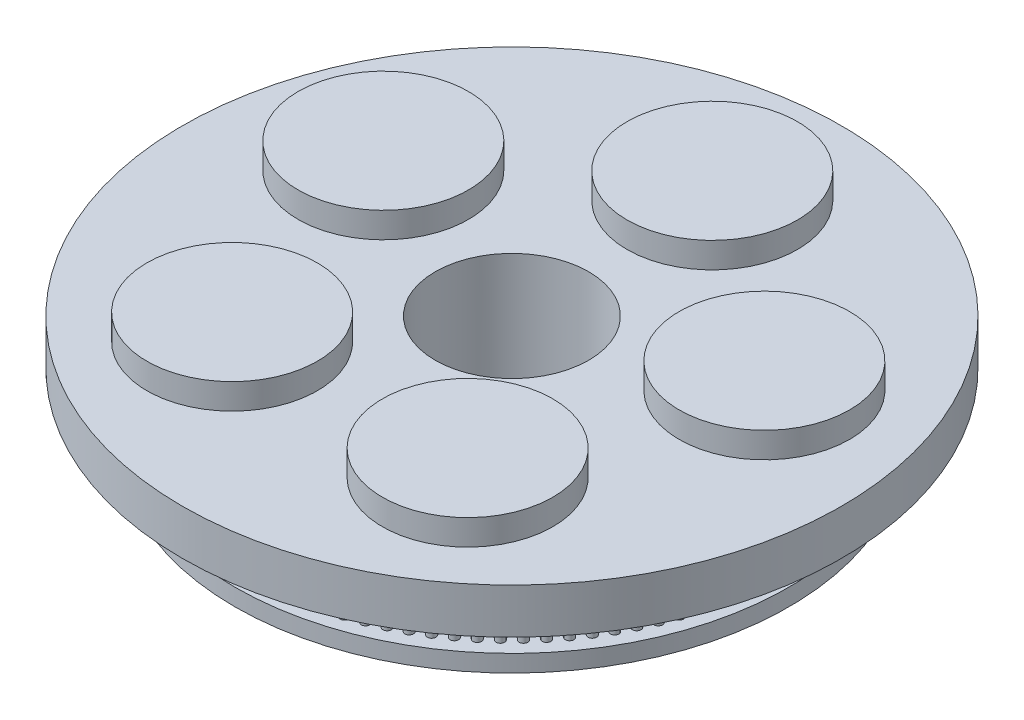
SolidWorks part; units mm, degrees
ref_plane "前基準面" through (0, 0, 0) normal (0, 0, 1) x (1, 0, 0)
ref_plane "上基準面" through (0, 0, 0) normal (0, 1, 0) x (1, 0, 0)
ref_plane "右基準面" through (0, 0, 0) normal (1, 0, 0) x (0, 0, -1)
sketch "草圖1" plane through (0, 0, 0) normal (0, 1, 0) x (1, 0, 0)
  circle A0 centre (0, 0) radius 38.66
  circle A1 centre (0, 0) radius 9
  dimension "D1" = 77.32
  dimension "D2" = 18
extrude "填料-伸長1" add sketch "草圖1" along normal blind 5.3
sketch "草圖3" plane through (0, 0, 0) normal (0, 0, 1) x (1, 0, 0)
  line L0 (0, 0) -> (0, 14.4931) construction
sketch "草圖2" plane through (0, 5.3, 0) normal (0, 1, 0) x (1, 0, 0)
  circle A0 centre (0, 23.5) radius 10
  dimension "D1" = 20
  dimension "D2" = 23.5
extrude "填料-伸長2" add sketch "草圖2" along normal blind 3
pattern_circular "環狀複製排列1" count 5 over 360 about axis through (0, 0, 0) along (0, 1, 0) of "填料-伸長2" reverse direction yes
sketch "草圖4" plane through (0, 0, 0) normal (0, -1, 0) x (1, 0, 0)
  line L0 (0, 0) -> (0, 38.66) construction
  line L1 (-0.5, 30.56) -> (-0.5, 29.9958) construction
  line L2 (-0.5, 30.56) -> (-0.5, 30.41)
  line L3 (0.5, 30.56) -> (0.5, 30.41)
  line L4 (1.4199, 30.5311) -> (1.4104, 30.3814)
  line L5 (2.4179, 30.4683) -> (2.4085, 30.3186)
  line L6 (3.3341, 30.3817) -> (3.3153, 30.2329)
  line L7 (4.3262, 30.2564) -> (4.3074, 30.1075)
  line L8 (5.2352, 30.1124) -> (5.2071, 29.965)
  line L9 (6.2175, 29.925) -> (6.1894, 29.7777)
  line L10 (7.1157, 29.7242) -> (7.0784, 29.579)
  line L11 (8.0843, 29.4756) -> (8.047, 29.3303)
  line L12 (8.968, 29.2188) -> (8.9217, 29.0761)
  line L13 (9.9191, 28.9098) -> (9.8727, 28.7671)
  line L14 (10.785, 28.598) -> (10.7298, 28.4586)
  line L15 (11.7148, 28.2299) -> (11.6596, 28.0904)
  line L16 (12.5594, 27.8644) -> (12.4955, 27.7287)
  line L17 (13.4642, 27.4386) -> (13.4004, 27.3029)
  line L18 (14.2842, 27.0208) -> (14.212, 26.8894)
  line L19 (15.1605, 26.5391) -> (15.0883, 26.4076)
  line L20 (15.9527, 26.0706) -> (15.8723, 25.9439)
  line L21 (16.797, 25.5347) -> (16.7167, 25.4081)
  line L22 (17.5582, 25.0175) -> (17.47, 24.8961)
  line L23 (18.3672, 24.4297) -> (18.2791, 24.3083)
  line L24 (19.0944, 23.8656) -> (18.9988, 23.75)
  line L25 (19.8649, 23.2282) -> (19.7693, 23.1126)
  line L26 (20.5553, 22.6196) -> (20.4526, 22.5102)
  line L27 (21.2842, 21.935) -> (21.1816, 21.8257)
  line L28 (21.935, 21.2842) -> (21.8257, 21.1816)
  line L29 (22.6196, 20.5553) -> (22.5102, 20.4526)
  line L30 (23.2282, 19.8649) -> (23.1126, 19.7693)
  line L31 (23.8656, 19.0944) -> (23.75, 18.9988)
  line L32 (24.4297, 18.3672) -> (24.3083, 18.2791)
  line L33 (25.0175, 17.5582) -> (24.8961, 17.47)
  line L34 (25.5347, 16.797) -> (25.4081, 16.7167)
  line L35 (26.0706, 15.9527) -> (25.9439, 15.8723)
  line L36 (26.5391, 15.1605) -> (26.4076, 15.0883)
  line L37 (27.0208, 14.2842) -> (26.8894, 14.212)
  line L38 (27.4386, 13.4642) -> (27.3029, 13.4004)
  line L39 (27.8644, 12.5594) -> (27.7287, 12.4955)
  line L40 (28.2299, 11.7148) -> (28.0904, 11.6596)
  line L41 (28.598, 10.785) -> (28.4586, 10.7298)
  line L42 (28.9098, 9.9191) -> (28.7671, 9.8727)
  line L43 (29.2188, 8.968) -> (29.0761, 8.9217)
  line L44 (29.4756, 8.0843) -> (29.3303, 8.047)
  line L45 (29.7242, 7.1157) -> (29.579, 7.0784)
  line L46 (29.925, 6.2175) -> (29.7777, 6.1894)
  line L47 (30.1124, 5.2352) -> (29.965, 5.2071)
  line L48 (30.2564, 4.3262) -> (30.1075, 4.3074)
  line L49 (30.3817, 3.3341) -> (30.2329, 3.3153)
  line L50 (30.4683, 2.4179) -> (30.3186, 2.4085)
  line L51 (30.5311, 1.4199) -> (30.3814, 1.4104)
  line L52 (30.56, 0.5) -> (30.41, 0.5)
  line L53 (30.56, -0.5) -> (30.41, -0.5)
  line L54 (30.5311, -1.4199) -> (30.3814, -1.4104)
  line L55 (30.4683, -2.4179) -> (30.3186, -2.4085)
  line L56 (30.3817, -3.3341) -> (30.2329, -3.3153)
  line L57 (30.2564, -4.3262) -> (30.1075, -4.3074)
  line L58 (30.1124, -5.2352) -> (29.965, -5.2071)
  line L59 (29.925, -6.2175) -> (29.7777, -6.1894)
  line L60 (29.7242, -7.1157) -> (29.579, -7.0784)
  line L61 (29.4756, -8.0843) -> (29.3303, -8.047)
  line L62 (29.2188, -8.968) -> (29.0761, -8.9217)
  line L63 (28.9098, -9.9191) -> (28.7671, -9.8727)
  line L64 (28.598, -10.785) -> (28.4586, -10.7298)
  line L65 (28.2299, -11.7148) -> (28.0904, -11.6596)
  line L66 (27.8644, -12.5594) -> (27.7287, -12.4955)
  line L67 (27.4386, -13.4642) -> (27.3029, -13.4004)
  line L68 (27.0208, -14.2842) -> (26.8894, -14.212)
  line L69 (26.5391, -15.1605) -> (26.4076, -15.0883)
  line L70 (26.0706, -15.9527) -> (25.9439, -15.8723)
  line L71 (25.5347, -16.797) -> (25.4081, -16.7167)
  line L72 (25.0175, -17.5582) -> (24.8961, -17.47)
  line L73 (24.4297, -18.3672) -> (24.3083, -18.2791)
  line L74 (23.8656, -19.0944) -> (23.75, -18.9988)
  line L75 (23.2282, -19.8649) -> (23.1126, -19.7693)
  line L76 (22.6196, -20.5553) -> (22.5102, -20.4526)
  line L77 (21.935, -21.2842) -> (21.8257, -21.1816)
  line L78 (21.2842, -21.935) -> (21.1816, -21.8257)
  line L79 (20.5553, -22.6196) -> (20.4526, -22.5102)
  line L80 (19.8649, -23.2282) -> (19.7693, -23.1126)
  line L81 (19.0944, -23.8656) -> (18.9988, -23.75)
  line L82 (18.3672, -24.4297) -> (18.2791, -24.3083)
  line L83 (17.5582, -25.0175) -> (17.47, -24.8961)
  line L84 (16.797, -25.5347) -> (16.7167, -25.4081)
  line L85 (15.9527, -26.0706) -> (15.8723, -25.9439)
  line L86 (15.1605, -26.5391) -> (15.0883, -26.4076)
  line L87 (14.2842, -27.0208) -> (14.212, -26.8894)
  line L88 (13.4642, -27.4386) -> (13.4004, -27.3029)
  line L89 (12.5594, -27.8644) -> (12.4955, -27.7287)
  line L90 (11.7148, -28.2299) -> (11.6596, -28.0904)
  line L91 (10.785, -28.598) -> (10.7298, -28.4586)
  line L92 (9.9191, -28.9098) -> (9.8727, -28.7671)
  line L93 (8.968, -29.2188) -> (8.9217, -29.0761)
  line L94 (8.0843, -29.4756) -> (8.047, -29.3303)
  line L95 (7.1157, -29.7242) -> (7.0784, -29.579)
  line L96 (6.2175, -29.925) -> (6.1894, -29.7777)
  line L97 (5.2352, -30.1124) -> (5.2071, -29.965)
  line L98 (4.3262, -30.2564) -> (4.3074, -30.1075)
  line L99 (3.3341, -30.3817) -> (3.3153, -30.2329)
  line L100 (2.4179, -30.4683) -> (2.4085, -30.3186)
  line L101 (1.4199, -30.5311) -> (1.4104, -30.3814)
  line L102 (0.5, -30.56) -> (0.5, -30.41)
  line L103 (-0.5, -30.56) -> (-0.5, -30.41)
  line L104 (-1.4199, -30.5311) -> (-1.4104, -30.3814)
  line L105 (-2.4179, -30.4683) -> (-2.4085, -30.3186)
  line L106 (-3.3341, -30.3817) -> (-3.3153, -30.2329)
  line L107 (-4.3262, -30.2564) -> (-4.3074, -30.1075)
  line L108 (-5.2352, -30.1124) -> (-5.2071, -29.965)
  line L109 (-6.2175, -29.925) -> (-6.1894, -29.7777)
  line L110 (-7.1157, -29.7242) -> (-7.0784, -29.579)
  line L111 (-8.0843, -29.4756) -> (-8.047, -29.3303)
  line L112 (-8.968, -29.2188) -> (-8.9217, -29.0761)
  line L113 (-9.9191, -28.9098) -> (-9.8727, -28.7671)
  line L114 (-10.785, -28.598) -> (-10.7298, -28.4586)
  line L115 (-11.7148, -28.2299) -> (-11.6596, -28.0904)
  line L116 (-12.5594, -27.8644) -> (-12.4955, -27.7287)
  line L117 (-13.4642, -27.4386) -> (-13.4004, -27.3029)
  line L118 (-14.2842, -27.0208) -> (-14.212, -26.8894)
  line L119 (-15.1605, -26.5391) -> (-15.0883, -26.4076)
  line L120 (-15.9527, -26.0706) -> (-15.8723, -25.9439)
  line L121 (-16.797, -25.5347) -> (-16.7167, -25.4081)
  line L122 (-17.5582, -25.0175) -> (-17.47, -24.8961)
  line L123 (-18.3672, -24.4297) -> (-18.2791, -24.3083)
  line L124 (-19.0944, -23.8656) -> (-18.9988, -23.75)
  line L125 (-19.8649, -23.2282) -> (-19.7693, -23.1126)
  line L126 (-20.5553, -22.6196) -> (-20.4526, -22.5102)
  line L127 (-21.2842, -21.935) -> (-21.1816, -21.8257)
  line L128 (-21.935, -21.2842) -> (-21.8257, -21.1816)
  line L129 (-22.6196, -20.5553) -> (-22.5102, -20.4526)
  line L130 (-23.2282, -19.8649) -> (-23.1126, -19.7693)
  line L131 (-23.8656, -19.0944) -> (-23.75, -18.9988)
  line L132 (-24.4297, -18.3672) -> (-24.3083, -18.2791)
  line L133 (-25.0175, -17.5582) -> (-24.8961, -17.47)
  line L134 (-25.5347, -16.797) -> (-25.4081, -16.7167)
  line L135 (-26.0706, -15.9527) -> (-25.9439, -15.8723)
  line L136 (-26.5391, -15.1605) -> (-26.4076, -15.0883)
  line L137 (-27.0208, -14.2842) -> (-26.8894, -14.212)
  line L138 (-27.4386, -13.4642) -> (-27.3029, -13.4004)
  line L139 (-27.8644, -12.5594) -> (-27.7287, -12.4955)
  line L140 (-28.2299, -11.7148) -> (-28.0904, -11.6596)
  line L141 (-28.598, -10.785) -> (-28.4586, -10.7298)
  line L142 (-28.9098, -9.9191) -> (-28.7671, -9.8727)
  line L143 (-29.2188, -8.968) -> (-29.0761, -8.9217)
  line L144 (-29.4756, -8.0843) -> (-29.3303, -8.047)
  line L145 (-29.7242, -7.1157) -> (-29.579, -7.0784)
  line L146 (-29.925, -6.2175) -> (-29.7777, -6.1894)
  line L147 (-30.1124, -5.2352) -> (-29.965, -5.2071)
  line L148 (-30.2564, -4.3262) -> (-30.1075, -4.3074)
  line L149 (-30.3817, -3.3341) -> (-30.2329, -3.3153)
  line L150 (-30.4683, -2.4179) -> (-30.3186, -2.4085)
  line L151 (-30.5311, -1.4199) -> (-30.3814, -1.4104)
  line L152 (-30.56, -0.5) -> (-30.41, -0.5)
  line L153 (-30.56, 0.5) -> (-30.41, 0.5)
  line L154 (-30.5311, 1.4199) -> (-30.3814, 1.4104)
  line L155 (-30.4683, 2.4179) -> (-30.3186, 2.4085)
  line L156 (-30.3817, 3.3341) -> (-30.2329, 3.3153)
  line L157 (-30.2564, 4.3262) -> (-30.1075, 4.3074)
  line L158 (-30.1124, 5.2352) -> (-29.965, 5.2071)
  line L159 (-29.925, 6.2175) -> (-29.7777, 6.1894)
  line L160 (-29.7242, 7.1157) -> (-29.579, 7.0784)
  line L161 (-29.4756, 8.0843) -> (-29.3303, 8.047)
  line L162 (-29.2188, 8.968) -> (-29.0761, 8.9217)
  line L163 (-28.9098, 9.9191) -> (-28.7671, 9.8727)
  line L164 (-28.598, 10.785) -> (-28.4586, 10.7298)
  line L165 (-28.2299, 11.7148) -> (-28.0904, 11.6596)
  line L166 (-27.8644, 12.5594) -> (-27.7287, 12.4955)
  line L167 (-27.4386, 13.4642) -> (-27.3029, 13.4004)
  line L168 (-27.0208, 14.2842) -> (-26.8894, 14.212)
  line L169 (-26.5391, 15.1605) -> (-26.4076, 15.0883)
  line L170 (-26.0706, 15.9527) -> (-25.9439, 15.8723)
  line L171 (-25.5347, 16.797) -> (-25.4081, 16.7167)
  line L172 (-25.0175, 17.5582) -> (-24.8961, 17.47)
  line L173 (-24.4297, 18.3672) -> (-24.3083, 18.2791)
  line L174 (-23.8656, 19.0944) -> (-23.75, 18.9988)
  line L175 (-23.2282, 19.8649) -> (-23.1126, 19.7693)
  line L176 (-22.6196, 20.5553) -> (-22.5102, 20.4526)
  line L177 (-21.935, 21.2842) -> (-21.8257, 21.1816)
  line L178 (-21.2842, 21.935) -> (-21.1816, 21.8257)
  line L179 (-20.5553, 22.6196) -> (-20.4526, 22.5102)
  line L180 (-19.8649, 23.2282) -> (-19.7693, 23.1126)
  line L181 (-19.0944, 23.8656) -> (-18.9988, 23.75)
  line L182 (-18.3672, 24.4297) -> (-18.2791, 24.3083)
  line L183 (-17.5582, 25.0175) -> (-17.47, 24.8961)
  line L184 (-16.797, 25.5347) -> (-16.7167, 25.4081)
  line L185 (-15.9527, 26.0706) -> (-15.8723, 25.9439)
  line L186 (-15.1605, 26.5391) -> (-15.0883, 26.4076)
  line L187 (-14.2842, 27.0208) -> (-14.212, 26.8894)
  line L188 (-13.4642, 27.4386) -> (-13.4004, 27.3029)
  line L189 (-12.5594, 27.8644) -> (-12.4955, 27.7287)
  line L190 (-11.7148, 28.2299) -> (-11.6596, 28.0904)
  line L191 (-10.785, 28.598) -> (-10.7298, 28.4586)
  line L192 (-9.9191, 28.9098) -> (-9.8727, 28.7671)
  line L193 (-8.968, 29.2188) -> (-8.9217, 29.0761)
  line L194 (-8.0843, 29.4756) -> (-8.047, 29.3303)
  line L195 (-7.1157, 29.7242) -> (-7.0784, 29.579)
  line L196 (-6.2175, 29.925) -> (-6.1894, 29.7777)
  line L197 (-5.2352, 30.1124) -> (-5.2071, 29.965)
  line L198 (-4.3262, 30.2564) -> (-4.3074, 30.1075)
  line L199 (-3.3341, 30.3817) -> (-3.3153, 30.2329)
  line L200 (-2.4179, 30.4683) -> (-2.4085, 30.3186)
  line L201 (-1.4199, 30.5311) -> (-1.4104, 30.3814)
  circle A0 centre (0, 0) radius 30.56 construction
  circle A1 centre (0, 0) radius 30
  circle A2 centre (0, 0) radius 38.66 construction
  arc A3 (0.5, 30.5559) -> (-0.5, 30.56) centre (0, 30.56) ccw
  arc A4 (-0.5, 30.41) -> (-0.9112, 29.9862) centre (-0.924, 30.41) cw
  arc A5 (2.4176, 30.4642) -> (1.4199, 30.5311) centre (1.9189, 30.4997) ccw
  arc A6 (1.4104, 30.3814) -> (0.9735, 29.9842) centre (0.9872, 30.408) cw
  arc A7 (0.5, 30.41) -> (0.9112, 29.9862) centre (0.924, 30.41) ccw
  arc A8 (2.4085, 30.3186) -> (2.7922, 29.8698) centre (2.8317, 30.292) ccw
  arc A9 (4.3257, 30.2523) -> (3.3341, 30.3817) centre (3.8302, 30.319) ccw
  arc A10 (3.3153, 30.2329) -> (2.8543, 29.8639) centre (2.8946, 30.286) cw
  arc A11 (4.3074, 30.1075) -> (4.6622, 29.6355) centre (4.7281, 30.0544) ccw
  arc A12 (6.2167, 29.921) -> (5.2352, 30.1124) centre (5.7264, 30.0187) ccw
  arc A13 (5.2071, 29.965) -> (4.7238, 29.6258) centre (4.7906, 30.0445) cw
  arc A14 (6.1894, 29.7777) -> (6.5139, 29.2843) centre (6.6059, 29.6982) ccw
  arc A15 (8.0832, 29.4716) -> (7.1157, 29.7242) centre (7.6, 29.5999) ccw
  arc A16 (7.0784, 29.579) -> (6.5747, 29.2707) centre (6.6677, 29.6844) cw
  arc A17 (8.047, 29.3303) -> (8.3398, 28.8175) centre (8.4577, 29.2248) ccw
  arc A18 (9.9178, 28.9059) -> (8.968, 29.2188) centre (9.4436, 29.0643) ccw
  arc A19 (8.9217, 29.0761) -> (8.3997, 28.8001) centre (8.5184, 29.2072) cw
  arc A20 (9.8727, 28.7671) -> (10.1328, 28.237) centre (10.276, 28.6361) ccw
  arc A21 (11.7133, 28.2261) -> (10.785, 28.598) centre (11.2499, 28.414) ccw
  arc A22 (10.7298, 28.4586) -> (10.1915, 28.2158) centre (10.3355, 28.6147) cw
  arc A23 (11.6596, 28.0904) -> (11.8858, 27.545) centre (12.0538, 27.9343) ccw
  arc A24 (13.4625, 27.4349) -> (12.5594, 27.8644) centre (13.0118, 27.6515) ccw
  arc A25 (12.4955, 27.7287) -> (11.943, 27.5202) centre (12.1119, 27.9092) cw
  arc A26 (13.4004, 27.3029) -> (13.5919, 26.7443) centre (13.784, 27.1224) ccw
  arc A27 (15.1586, 26.5355) -> (14.2842, 27.0208) centre (14.7224, 26.7799) ccw
  arc A28 (14.212, 26.8894) -> (13.6475, 26.716) centre (13.8404, 27.0936) cw
  arc A29 (15.0883, 26.4076) -> (15.2444, 25.8381) centre (15.4599, 26.2033) ccw
  arc A30 (16.7948, 25.5313) -> (15.9527, 26.0706) centre (16.3749, 25.8027) ccw
  arc A31 (15.8723, 25.9439) -> (15.2981, 25.8064) centre (15.5143, 26.1711) cw
  arc A32 (16.7167, 25.4081) -> (16.8367, 24.8299) centre (17.0747, 25.1809) ccw
  arc A33 (18.3648, 24.4264) -> (17.5582, 25.0175) centre (17.9627, 24.7236) ccw
  arc A34 (17.47, 24.8961) -> (16.8883, 24.7949) centre (17.127, 25.1453) cw
  arc A35 (18.2791, 24.3083) -> (18.3626, 23.7237) centre (18.6221, 24.0591) ccw
  arc A36 (19.8623, 23.225) -> (19.0944, 23.8656) centre (19.4797, 23.5469) ccw
  arc A37 (18.9988, 23.75) -> (18.4118, 23.6855) centre (18.6721, 24.0203) cw
  arc A38 (19.7693, 23.1126) -> (19.816, 22.5239) centre (20.096, 22.8423) ccw
  arc A39 (21.2814, 21.932) -> (20.5553, 22.6196) centre (20.9198, 22.2773) ccw
  arc A40 (20.4526, 22.5102) -> (19.8627, 22.4827) centre (20.1435, 22.8005) cw
  arc A41 (21.1816, 21.8257) -> (21.1911, 21.2352) centre (21.4907, 21.5354) ccw
  arc A42 (22.6166, 20.5525) -> (21.935, 21.2842) centre (22.2773, 20.9198) ccw
  arc A43 (21.8257, 21.1816) -> (21.2352, 21.1911) centre (21.5354, 21.4907) cw
  arc A44 (22.5102, 20.4526) -> (22.4827, 19.8627) centre (22.8005, 20.1435) ccw
  arc A45 (23.8624, 19.0918) -> (23.2282, 19.8649) centre (23.5469, 19.4797) ccw
  arc A46 (23.1126, 19.7693) -> (22.5239, 19.816) centre (22.8423, 20.096) cw
  arc A47 (23.75, 18.9988) -> (23.6855, 18.4118) centre (24.0203, 18.6721) ccw
  arc A48 (25.0141, 17.5558) -> (24.4297, 18.3672) centre (24.7236, 17.9627) ccw
  arc A49 (24.3083, 18.2791) -> (23.7237, 18.3626) centre (24.0591, 18.6221) cw
  arc A50 (24.8961, 17.47) -> (24.7949, 16.8883) centre (25.1453, 17.127) ccw
  arc A51 (26.0671, 15.9505) -> (25.5347, 16.797) centre (25.8027, 16.3749) ccw
  arc A52 (25.4081, 16.7167) -> (24.8299, 16.8367) centre (25.1809, 17.0747) cw
  arc A53 (25.9439, 15.8723) -> (25.8064, 15.2981) centre (26.1711, 15.5143) ccw
  arc A54 (27.0172, 14.2823) -> (26.5391, 15.1605) centre (26.7799, 14.7224) ccw
  arc A55 (26.4076, 15.0883) -> (25.8381, 15.2444) centre (26.2033, 15.4599) cw
  arc A56 (26.8894, 14.212) -> (26.716, 13.6475) centre (27.0936, 13.8404) ccw
  arc A57 (27.8607, 12.5577) -> (27.4386, 13.4642) centre (27.6515, 13.0118) ccw
  arc A58 (27.3029, 13.4004) -> (26.7443, 13.5919) centre (27.1224, 13.784) cw
  arc A59 (27.7287, 12.4955) -> (27.5202, 11.943) centre (27.9092, 12.1119) ccw
  arc A60 (28.5942, 10.7835) -> (28.2299, 11.7148) centre (28.414, 11.2499) ccw
  arc A61 (28.0904, 11.6596) -> (27.545, 11.8858) centre (27.9343, 12.0538) cw
  arc A62 (28.4586, 10.7298) -> (28.2158, 10.1915) centre (28.6147, 10.3355) ccw
  arc A63 (29.2149, 8.9668) -> (28.9098, 9.9191) centre (29.0643, 9.4436) ccw
  arc A64 (28.7671, 9.8727) -> (28.237, 10.1328) centre (28.6361, 10.276) cw
  arc A65 (29.0761, 8.9217) -> (28.8001, 8.3997) centre (29.2072, 8.5184) ccw
  arc A66 (29.7203, 7.1147) -> (29.4756, 8.0843) centre (29.5999, 7.6) ccw
  arc A67 (29.3303, 8.047) -> (28.8175, 8.3398) centre (29.2248, 8.4577) cw
  arc A68 (29.579, 7.0784) -> (29.2707, 6.5747) centre (29.6844, 6.6677) ccw
  arc A69 (30.1084, 5.2345) -> (29.925, 6.2175) centre (30.0187, 5.7264) ccw
  arc A70 (29.7777, 6.1894) -> (29.2843, 6.5139) centre (29.6982, 6.6059) cw
  arc A71 (29.965, 5.2071) -> (29.6258, 4.7238) centre (30.0445, 4.7906) ccw
  arc A72 (30.3776, 3.3336) -> (30.2564, 4.3262) centre (30.319, 3.8302) ccw
  arc A73 (30.1075, 4.3074) -> (29.6355, 4.6622) centre (30.0544, 4.7281) cw
  arc A74 (30.2329, 3.3153) -> (29.8639, 2.8543) centre (30.286, 2.8946) ccw
  arc A75 (30.527, 1.4196) -> (30.4683, 2.4179) centre (30.4997, 1.9189) ccw
  arc A76 (30.3186, 2.4085) -> (29.8698, 2.7922) centre (30.292, 2.8317) cw
  arc A77 (30.3814, 1.4104) -> (29.9842, 0.9735) centre (30.408, 0.9872) ccw
  arc A78 (30.5559, -0.5) -> (30.56, 0.5) centre (30.56, 0) ccw
  arc A79 (30.41, 0.5) -> (29.9862, 0.9112) centre (30.41, 0.924) cw
  arc A80 (30.41, -0.5) -> (29.9862, -0.9112) centre (30.41, -0.924) ccw
  arc A81 (30.4642, -2.4176) -> (30.5311, -1.4199) centre (30.4997, -1.9189) ccw
  arc A82 (30.3814, -1.4104) -> (29.9842, -0.9735) centre (30.408, -0.9872) cw
  arc A83 (30.3186, -2.4085) -> (29.8698, -2.7922) centre (30.292, -2.8317) ccw
  arc A84 (30.2523, -4.3257) -> (30.3817, -3.3341) centre (30.319, -3.8302) ccw
  arc A85 (30.2329, -3.3153) -> (29.8639, -2.8543) centre (30.286, -2.8946) cw
  arc A86 (30.1075, -4.3074) -> (29.6355, -4.6622) centre (30.0544, -4.7281) ccw
  arc A87 (29.921, -6.2167) -> (30.1124, -5.2352) centre (30.0187, -5.7264) ccw
  arc A88 (29.965, -5.2071) -> (29.6258, -4.7238) centre (30.0445, -4.7906) cw
  arc A89 (29.7777, -6.1894) -> (29.2843, -6.5139) centre (29.6982, -6.6059) ccw
  arc A90 (29.4716, -8.0832) -> (29.7242, -7.1157) centre (29.5999, -7.6) ccw
  arc A91 (29.579, -7.0784) -> (29.2707, -6.5747) centre (29.6844, -6.6677) cw
  arc A92 (29.3303, -8.047) -> (28.8175, -8.3398) centre (29.2248, -8.4577) ccw
  arc A93 (28.9059, -9.9178) -> (29.2188, -8.968) centre (29.0643, -9.4436) ccw
  arc A94 (29.0761, -8.9217) -> (28.8001, -8.3997) centre (29.2072, -8.5184) cw
  arc A95 (28.7671, -9.8727) -> (28.237, -10.1328) centre (28.6361, -10.276) ccw
  arc A96 (28.2261, -11.7133) -> (28.598, -10.785) centre (28.414, -11.2499) ccw
  arc A97 (28.4586, -10.7298) -> (28.2158, -10.1915) centre (28.6147, -10.3355) cw
  arc A98 (28.0904, -11.6596) -> (27.545, -11.8858) centre (27.9343, -12.0538) ccw
  arc A99 (27.4349, -13.4625) -> (27.8644, -12.5594) centre (27.6515, -13.0118) ccw
  arc A100 (27.7287, -12.4955) -> (27.5202, -11.943) centre (27.9092, -12.1119) cw
  arc A101 (27.3029, -13.4004) -> (26.7443, -13.5919) centre (27.1224, -13.784) ccw
  arc A102 (26.5355, -15.1586) -> (27.0208, -14.2842) centre (26.7799, -14.7224) ccw
  arc A103 (26.8894, -14.212) -> (26.716, -13.6475) centre (27.0936, -13.8404) cw
  arc A104 (26.4076, -15.0883) -> (25.8381, -15.2444) centre (26.2033, -15.4599) ccw
  arc A105 (25.5313, -16.7948) -> (26.0706, -15.9527) centre (25.8027, -16.3749) ccw
  arc A106 (25.9439, -15.8723) -> (25.8064, -15.2981) centre (26.1711, -15.5143) cw
  arc A107 (25.4081, -16.7167) -> (24.8299, -16.8367) centre (25.1809, -17.0747) ccw
  arc A108 (24.4264, -18.3648) -> (25.0175, -17.5582) centre (24.7236, -17.9627) ccw
  arc A109 (24.8961, -17.47) -> (24.7949, -16.8883) centre (25.1453, -17.127) cw
  arc A110 (24.3083, -18.2791) -> (23.7237, -18.3626) centre (24.0591, -18.6221) ccw
  arc A111 (23.225, -19.8623) -> (23.8656, -19.0944) centre (23.5469, -19.4797) ccw
  arc A112 (23.75, -18.9988) -> (23.6855, -18.4118) centre (24.0203, -18.6721) cw
  arc A113 (23.1126, -19.7693) -> (22.5239, -19.816) centre (22.8423, -20.096) ccw
  arc A114 (21.932, -21.2814) -> (22.6196, -20.5553) centre (22.2773, -20.9198) ccw
  arc A115 (22.5102, -20.4526) -> (22.4827, -19.8627) centre (22.8005, -20.1435) cw
  arc A116 (21.8257, -21.1816) -> (21.2352, -21.1911) centre (21.5354, -21.4907) ccw
  arc A117 (20.5525, -22.6166) -> (21.2842, -21.935) centre (20.9198, -22.2773) ccw
  arc A118 (21.1816, -21.8257) -> (21.1911, -21.2352) centre (21.4907, -21.5354) cw
  arc A119 (20.4526, -22.5102) -> (19.8627, -22.4827) centre (20.1435, -22.8005) ccw
  arc A120 (19.0918, -23.8624) -> (19.8649, -23.2282) centre (19.4797, -23.5469) ccw
  arc A121 (19.7693, -23.1126) -> (19.816, -22.5239) centre (20.096, -22.8423) cw
  arc A122 (18.9988, -23.75) -> (18.4118, -23.6855) centre (18.6721, -24.0203) ccw
  arc A123 (17.5558, -25.0141) -> (18.3672, -24.4297) centre (17.9627, -24.7236) ccw
  arc A124 (18.2791, -24.3083) -> (18.3626, -23.7237) centre (18.6221, -24.0591) cw
  arc A125 (17.47, -24.8961) -> (16.8883, -24.7949) centre (17.127, -25.1453) ccw
  arc A126 (15.9505, -26.0671) -> (16.797, -25.5347) centre (16.3749, -25.8027) ccw
  arc A127 (16.7167, -25.4081) -> (16.8367, -24.8299) centre (17.0747, -25.1809) cw
  arc A128 (15.8723, -25.9439) -> (15.2981, -25.8064) centre (15.5143, -26.1711) ccw
  arc A129 (14.2823, -27.0172) -> (15.1605, -26.5391) centre (14.7224, -26.7799) ccw
  arc A130 (15.0883, -26.4076) -> (15.2444, -25.8381) centre (15.4599, -26.2033) cw
  arc A131 (14.212, -26.8894) -> (13.6475, -26.716) centre (13.8404, -27.0936) ccw
  arc A132 (12.5577, -27.8607) -> (13.4642, -27.4386) centre (13.0118, -27.6515) ccw
  arc A133 (13.4004, -27.3029) -> (13.5919, -26.7443) centre (13.784, -27.1224) cw
  arc A134 (12.4955, -27.7287) -> (11.943, -27.5202) centre (12.1119, -27.9092) ccw
  arc A135 (10.7835, -28.5942) -> (11.7148, -28.2299) centre (11.2499, -28.414) ccw
  arc A136 (11.6596, -28.0904) -> (11.8858, -27.545) centre (12.0538, -27.9343) cw
  arc A137 (10.7298, -28.4586) -> (10.1915, -28.2158) centre (10.3355, -28.6147) ccw
  arc A138 (8.9668, -29.2149) -> (9.9191, -28.9098) centre (9.4436, -29.0643) ccw
  arc A139 (9.8727, -28.7671) -> (10.1328, -28.237) centre (10.276, -28.6361) cw
  arc A140 (8.9217, -29.0761) -> (8.3997, -28.8001) centre (8.5184, -29.2072) ccw
  arc A141 (7.1147, -29.7203) -> (8.0843, -29.4756) centre (7.6, -29.5999) ccw
  arc A142 (8.047, -29.3303) -> (8.3398, -28.8175) centre (8.4577, -29.2248) cw
  arc A143 (7.0784, -29.579) -> (6.5747, -29.2707) centre (6.6677, -29.6844) ccw
  arc A144 (5.2345, -30.1084) -> (6.2175, -29.925) centre (5.7264, -30.0187) ccw
  arc A145 (6.1894, -29.7777) -> (6.5139, -29.2843) centre (6.6059, -29.6982) cw
  arc A146 (5.2071, -29.965) -> (4.7238, -29.6258) centre (4.7906, -30.0445) ccw
  arc A147 (3.3336, -30.3776) -> (4.3262, -30.2564) centre (3.8302, -30.319) ccw
  arc A148 (4.3074, -30.1075) -> (4.6622, -29.6355) centre (4.7281, -30.0544) cw
  arc A149 (3.3153, -30.2329) -> (2.8543, -29.8639) centre (2.8946, -30.286) ccw
  arc A150 (1.4196, -30.527) -> (2.4179, -30.4683) centre (1.9189, -30.4997) ccw
  arc A151 (2.4085, -30.3186) -> (2.7922, -29.8698) centre (2.8317, -30.292) cw
  arc A152 (1.4104, -30.3814) -> (0.9735, -29.9842) centre (0.9872, -30.408) ccw
  arc A153 (-0.5, -30.5559) -> (0.5, -30.56) centre (0, -30.56) ccw
  arc A154 (0.5, -30.41) -> (0.9112, -29.9862) centre (0.924, -30.41) cw
  arc A155 (-0.5, -30.41) -> (-0.9112, -29.9862) centre (-0.924, -30.41) ccw
  arc A156 (-2.4176, -30.4642) -> (-1.4199, -30.5311) centre (-1.9189, -30.4997) ccw
  arc A157 (-1.4104, -30.3814) -> (-0.9735, -29.9842) centre (-0.9872, -30.408) cw
  arc A158 (-2.4085, -30.3186) -> (-2.7922, -29.8698) centre (-2.8317, -30.292) ccw
  arc A159 (-4.3257, -30.2523) -> (-3.3341, -30.3817) centre (-3.8302, -30.319) ccw
  arc A160 (-3.3153, -30.2329) -> (-2.8543, -29.8639) centre (-2.8946, -30.286) cw
  arc A161 (-4.3074, -30.1075) -> (-4.6622, -29.6355) centre (-4.7281, -30.0544) ccw
  arc A162 (-6.2167, -29.921) -> (-5.2352, -30.1124) centre (-5.7264, -30.0187) ccw
  arc A163 (-5.2071, -29.965) -> (-4.7238, -29.6258) centre (-4.7906, -30.0445) cw
  arc A164 (-6.1894, -29.7777) -> (-6.5139, -29.2843) centre (-6.6059, -29.6982) ccw
  arc A165 (-8.0832, -29.4716) -> (-7.1157, -29.7242) centre (-7.6, -29.5999) ccw
  arc A166 (-7.0784, -29.579) -> (-6.5747, -29.2707) centre (-6.6677, -29.6844) cw
  arc A167 (-8.047, -29.3303) -> (-8.3398, -28.8175) centre (-8.4577, -29.2248) ccw
  arc A168 (-9.9178, -28.9059) -> (-8.968, -29.2188) centre (-9.4436, -29.0643) ccw
  arc A169 (-8.9217, -29.0761) -> (-8.3997, -28.8001) centre (-8.5184, -29.2072) cw
  arc A170 (-9.8727, -28.7671) -> (-10.1328, -28.237) centre (-10.276, -28.6361) ccw
  arc A171 (-11.7133, -28.2261) -> (-10.785, -28.598) centre (-11.2499, -28.414) ccw
  arc A172 (-10.7298, -28.4586) -> (-10.1915, -28.2158) centre (-10.3355, -28.6147) cw
  arc A173 (-11.6596, -28.0904) -> (-11.8858, -27.545) centre (-12.0538, -27.9343) ccw
  arc A174 (-13.4625, -27.4349) -> (-12.5594, -27.8644) centre (-13.0118, -27.6515) ccw
  arc A175 (-12.4955, -27.7287) -> (-11.943, -27.5202) centre (-12.1119, -27.9092) cw
  arc A176 (-13.4004, -27.3029) -> (-13.5919, -26.7443) centre (-13.784, -27.1224) ccw
  arc A177 (-15.1586, -26.5355) -> (-14.2842, -27.0208) centre (-14.7224, -26.7799) ccw
  arc A178 (-14.212, -26.8894) -> (-13.6475, -26.716) centre (-13.8404, -27.0936) cw
  arc A179 (-15.0883, -26.4076) -> (-15.2444, -25.8381) centre (-15.4599, -26.2033) ccw
  arc A180 (-16.7948, -25.5313) -> (-15.9527, -26.0706) centre (-16.3749, -25.8027) ccw
  arc A181 (-15.8723, -25.9439) -> (-15.2981, -25.8064) centre (-15.5143, -26.1711) cw
  arc A182 (-16.7167, -25.4081) -> (-16.8367, -24.8299) centre (-17.0747, -25.1809) ccw
  arc A183 (-18.3648, -24.4264) -> (-17.5582, -25.0175) centre (-17.9627, -24.7236) ccw
  arc A184 (-17.47, -24.8961) -> (-16.8883, -24.7949) centre (-17.127, -25.1453) cw
  arc A185 (-18.2791, -24.3083) -> (-18.3626, -23.7237) centre (-18.6221, -24.0591) ccw
  arc A186 (-19.8623, -23.225) -> (-19.0944, -23.8656) centre (-19.4797, -23.5469) ccw
  arc A187 (-18.9988, -23.75) -> (-18.4118, -23.6855) centre (-18.6721, -24.0203) cw
  arc A188 (-19.7693, -23.1126) -> (-19.816, -22.5239) centre (-20.096, -22.8423) ccw
  arc A189 (-21.2814, -21.932) -> (-20.5553, -22.6196) centre (-20.9198, -22.2773) ccw
  arc A190 (-20.4526, -22.5102) -> (-19.8627, -22.4827) centre (-20.1435, -22.8005) cw
  arc A191 (-21.1816, -21.8257) -> (-21.1911, -21.2352) centre (-21.4907, -21.5354) ccw
  arc A192 (-22.6166, -20.5525) -> (-21.935, -21.2842) centre (-22.2773, -20.9198) ccw
  arc A193 (-21.8257, -21.1816) -> (-21.2352, -21.1911) centre (-21.5354, -21.4907) cw
  arc A194 (-22.5102, -20.4526) -> (-22.4827, -19.8627) centre (-22.8005, -20.1435) ccw
  arc A195 (-23.8624, -19.0918) -> (-23.2282, -19.8649) centre (-23.5469, -19.4797) ccw
  arc A196 (-23.1126, -19.7693) -> (-22.5239, -19.816) centre (-22.8423, -20.096) cw
  arc A197 (-23.75, -18.9988) -> (-23.6855, -18.4118) centre (-24.0203, -18.6721) ccw
  arc A198 (-25.0141, -17.5558) -> (-24.4297, -18.3672) centre (-24.7236, -17.9627) ccw
  arc A199 (-24.3083, -18.2791) -> (-23.7237, -18.3626) centre (-24.0591, -18.6221) cw
  arc A200 (-24.8961, -17.47) -> (-24.7949, -16.8883) centre (-25.1453, -17.127) ccw
  arc A201 (-26.0671, -15.9505) -> (-25.5347, -16.797) centre (-25.8027, -16.3749) ccw
  arc A202 (-25.4081, -16.7167) -> (-24.8299, -16.8367) centre (-25.1809, -17.0747) cw
  arc A203 (-25.9439, -15.8723) -> (-25.8064, -15.2981) centre (-26.1711, -15.5143) ccw
  arc A204 (-27.0172, -14.2823) -> (-26.5391, -15.1605) centre (-26.7799, -14.7224) ccw
  arc A205 (-26.4076, -15.0883) -> (-25.8381, -15.2444) centre (-26.2033, -15.4599) cw
  arc A206 (-26.8894, -14.212) -> (-26.716, -13.6475) centre (-27.0936, -13.8404) ccw
  arc A207 (-27.8607, -12.5577) -> (-27.4386, -13.4642) centre (-27.6515, -13.0118) ccw
  arc A208 (-27.3029, -13.4004) -> (-26.7443, -13.5919) centre (-27.1224, -13.784) cw
  arc A209 (-27.7287, -12.4955) -> (-27.5202, -11.943) centre (-27.9092, -12.1119) ccw
  arc A210 (-28.5942, -10.7835) -> (-28.2299, -11.7148) centre (-28.414, -11.2499) ccw
  arc A211 (-28.0904, -11.6596) -> (-27.545, -11.8858) centre (-27.9343, -12.0538) cw
  arc A212 (-28.4586, -10.7298) -> (-28.2158, -10.1915) centre (-28.6147, -10.3355) ccw
  arc A213 (-29.2149, -8.9668) -> (-28.9098, -9.9191) centre (-29.0643, -9.4436) ccw
  arc A214 (-28.7671, -9.8727) -> (-28.237, -10.1328) centre (-28.6361, -10.276) cw
  arc A215 (-29.0761, -8.9217) -> (-28.8001, -8.3997) centre (-29.2072, -8.5184) ccw
  arc A216 (-29.7203, -7.1147) -> (-29.4756, -8.0843) centre (-29.5999, -7.6) ccw
  arc A217 (-29.3303, -8.047) -> (-28.8175, -8.3398) centre (-29.2248, -8.4577) cw
  arc A218 (-29.579, -7.0784) -> (-29.2707, -6.5747) centre (-29.6844, -6.6677) ccw
  arc A219 (-30.1084, -5.2345) -> (-29.925, -6.2175) centre (-30.0187, -5.7264) ccw
  arc A220 (-29.7777, -6.1894) -> (-29.2843, -6.5139) centre (-29.6982, -6.6059) cw
  arc A221 (-29.965, -5.2071) -> (-29.6258, -4.7238) centre (-30.0445, -4.7906) ccw
  arc A222 (-30.3776, -3.3336) -> (-30.2564, -4.3262) centre (-30.319, -3.8302) ccw
  arc A223 (-30.1075, -4.3074) -> (-29.6355, -4.6622) centre (-30.0544, -4.7281) cw
  arc A224 (-30.2329, -3.3153) -> (-29.8639, -2.8543) centre (-30.286, -2.8946) ccw
  arc A225 (-30.527, -1.4196) -> (-30.4683, -2.4179) centre (-30.4997, -1.9189) ccw
  arc A226 (-30.3186, -2.4085) -> (-29.8698, -2.7922) centre (-30.292, -2.8317) cw
  arc A227 (-30.3814, -1.4104) -> (-29.9842, -0.9735) centre (-30.408, -0.9872) ccw
  arc A228 (-30.5559, 0.5) -> (-30.56, -0.5) centre (-30.56, 0) ccw
  arc A229 (-30.41, -0.5) -> (-29.9862, -0.9112) centre (-30.41, -0.924) cw
  arc A230 (-30.41, 0.5) -> (-29.9862, 0.9112) centre (-30.41, 0.924) ccw
  arc A231 (-30.4642, 2.4176) -> (-30.5311, 1.4199) centre (-30.4997, 1.9189) ccw
  arc A232 (-30.3814, 1.4104) -> (-29.9842, 0.9735) centre (-30.408, 0.9872) cw
  arc A233 (-30.3186, 2.4085) -> (-29.8698, 2.7922) centre (-30.292, 2.8317) ccw
  arc A234 (-30.2523, 4.3257) -> (-30.3817, 3.3341) centre (-30.319, 3.8302) ccw
  arc A235 (-30.2329, 3.3153) -> (-29.8639, 2.8543) centre (-30.286, 2.8946) cw
  arc A236 (-30.1075, 4.3074) -> (-29.6355, 4.6622) centre (-30.0544, 4.7281) ccw
  arc A237 (-29.921, 6.2167) -> (-30.1124, 5.2352) centre (-30.0187, 5.7264) ccw
  arc A238 (-29.965, 5.2071) -> (-29.6258, 4.7238) centre (-30.0445, 4.7906) cw
  arc A239 (-29.7777, 6.1894) -> (-29.2843, 6.5139) centre (-29.6982, 6.6059) ccw
  arc A240 (-29.4716, 8.0832) -> (-29.7242, 7.1157) centre (-29.5999, 7.6) ccw
  arc A241 (-29.579, 7.0784) -> (-29.2707, 6.5747) centre (-29.6844, 6.6677) cw
  arc A242 (-29.3303, 8.047) -> (-28.8175, 8.3398) centre (-29.2248, 8.4577) ccw
  arc A243 (-28.9059, 9.9178) -> (-29.2188, 8.968) centre (-29.0643, 9.4436) ccw
  arc A244 (-29.0761, 8.9217) -> (-28.8001, 8.3997) centre (-29.2072, 8.5184) cw
  arc A245 (-28.7671, 9.8727) -> (-28.237, 10.1328) centre (-28.6361, 10.276) ccw
  arc A246 (-28.2261, 11.7133) -> (-28.598, 10.785) centre (-28.414, 11.2499) ccw
  arc A247 (-28.4586, 10.7298) -> (-28.2158, 10.1915) centre (-28.6147, 10.3355) cw
  arc A248 (-28.0904, 11.6596) -> (-27.545, 11.8858) centre (-27.9343, 12.0538) ccw
  arc A249 (-27.4349, 13.4625) -> (-27.8644, 12.5594) centre (-27.6515, 13.0118) ccw
  arc A250 (-27.7287, 12.4955) -> (-27.5202, 11.943) centre (-27.9092, 12.1119) cw
  arc A251 (-27.3029, 13.4004) -> (-26.7443, 13.5919) centre (-27.1224, 13.784) ccw
  arc A252 (-26.5355, 15.1586) -> (-27.0208, 14.2842) centre (-26.7799, 14.7224) ccw
  arc A253 (-26.8894, 14.212) -> (-26.716, 13.6475) centre (-27.0936, 13.8404) cw
  arc A254 (-26.4076, 15.0883) -> (-25.8381, 15.2444) centre (-26.2033, 15.4599) ccw
  arc A255 (-25.5313, 16.7948) -> (-26.0706, 15.9527) centre (-25.8027, 16.3749) ccw
  arc A256 (-25.9439, 15.8723) -> (-25.8064, 15.2981) centre (-26.1711, 15.5143) cw
  arc A257 (-25.4081, 16.7167) -> (-24.8299, 16.8367) centre (-25.1809, 17.0747) ccw
  arc A258 (-24.4264, 18.3648) -> (-25.0175, 17.5582) centre (-24.7236, 17.9627) ccw
  arc A259 (-24.8961, 17.47) -> (-24.7949, 16.8883) centre (-25.1453, 17.127) cw
  arc A260 (-24.3083, 18.2791) -> (-23.7237, 18.3626) centre (-24.0591, 18.6221) ccw
  arc A261 (-23.225, 19.8623) -> (-23.8656, 19.0944) centre (-23.5469, 19.4797) ccw
  arc A262 (-23.75, 18.9988) -> (-23.6855, 18.4118) centre (-24.0203, 18.6721) cw
  arc A263 (-23.1126, 19.7693) -> (-22.5239, 19.816) centre (-22.8423, 20.096) ccw
  arc A264 (-21.932, 21.2814) -> (-22.6196, 20.5553) centre (-22.2773, 20.9198) ccw
  arc A265 (-22.5102, 20.4526) -> (-22.4827, 19.8627) centre (-22.8005, 20.1435) cw
  arc A266 (-21.8257, 21.1816) -> (-21.2352, 21.1911) centre (-21.5354, 21.4907) ccw
  arc A267 (-20.5525, 22.6166) -> (-21.2842, 21.935) centre (-20.9198, 22.2773) ccw
  arc A268 (-21.1816, 21.8257) -> (-21.1911, 21.2352) centre (-21.4907, 21.5354) cw
  arc A269 (-20.4526, 22.5102) -> (-19.8627, 22.4827) centre (-20.1435, 22.8005) ccw
  arc A270 (-19.0918, 23.8624) -> (-19.8649, 23.2282) centre (-19.4797, 23.5469) ccw
  arc A271 (-19.7693, 23.1126) -> (-19.816, 22.5239) centre (-20.096, 22.8423) cw
  arc A272 (-18.9988, 23.75) -> (-18.4118, 23.6855) centre (-18.6721, 24.0203) ccw
  arc A273 (-17.5558, 25.0141) -> (-18.3672, 24.4297) centre (-17.9627, 24.7236) ccw
  arc A274 (-18.2791, 24.3083) -> (-18.3626, 23.7237) centre (-18.6221, 24.0591) cw
  arc A275 (-17.47, 24.8961) -> (-16.8883, 24.7949) centre (-17.127, 25.1453) ccw
  arc A276 (-15.9505, 26.0671) -> (-16.797, 25.5347) centre (-16.3749, 25.8027) ccw
  arc A277 (-16.7167, 25.4081) -> (-16.8367, 24.8299) centre (-17.0747, 25.1809) cw
  arc A278 (-15.8723, 25.9439) -> (-15.2981, 25.8064) centre (-15.5143, 26.1711) ccw
  arc A279 (-14.2823, 27.0172) -> (-15.1605, 26.5391) centre (-14.7224, 26.7799) ccw
  arc A280 (-15.0883, 26.4076) -> (-15.2444, 25.8381) centre (-15.4599, 26.2033) cw
  arc A281 (-14.212, 26.8894) -> (-13.6475, 26.716) centre (-13.8404, 27.0936) ccw
  arc A282 (-12.5577, 27.8607) -> (-13.4642, 27.4386) centre (-13.0118, 27.6515) ccw
  arc A283 (-13.4004, 27.3029) -> (-13.5919, 26.7443) centre (-13.784, 27.1224) cw
  arc A284 (-12.4955, 27.7287) -> (-11.943, 27.5202) centre (-12.1119, 27.9092) ccw
  arc A285 (-10.7835, 28.5942) -> (-11.7148, 28.2299) centre (-11.2499, 28.414) ccw
  arc A286 (-11.6596, 28.0904) -> (-11.8858, 27.545) centre (-12.0538, 27.9343) cw
  arc A287 (-10.7298, 28.4586) -> (-10.1915, 28.2158) centre (-10.3355, 28.6147) ccw
  arc A288 (-8.9668, 29.2149) -> (-9.9191, 28.9098) centre (-9.4436, 29.0643) ccw
  arc A289 (-9.8727, 28.7671) -> (-10.1328, 28.237) centre (-10.276, 28.6361) cw
  arc A290 (-8.9217, 29.0761) -> (-8.3997, 28.8001) centre (-8.5184, 29.2072) ccw
  arc A291 (-7.1147, 29.7203) -> (-8.0843, 29.4756) centre (-7.6, 29.5999) ccw
  arc A292 (-8.047, 29.3303) -> (-8.3398, 28.8175) centre (-8.4577, 29.2248) cw
  arc A293 (-7.0784, 29.579) -> (-6.5747, 29.2707) centre (-6.6677, 29.6844) ccw
  arc A294 (-5.2345, 30.1084) -> (-6.2175, 29.925) centre (-5.7264, 30.0187) ccw
  arc A295 (-6.1894, 29.7777) -> (-6.5139, 29.2843) centre (-6.6059, 29.6982) cw
  arc A296 (-5.2071, 29.965) -> (-4.7238, 29.6258) centre (-4.7906, 30.0445) ccw
  arc A297 (-3.3336, 30.3776) -> (-4.3262, 30.2564) centre (-3.8302, 30.319) ccw
  arc A298 (-4.3074, 30.1075) -> (-4.6622, 29.6355) centre (-4.7281, 30.0544) cw
  arc A299 (-3.3153, 30.2329) -> (-2.8543, 29.8639) centre (-2.8946, 30.286) ccw
  arc A300 (-1.4196, 30.527) -> (-2.4179, 30.4683) centre (-1.9189, 30.4997) ccw
  arc A301 (-2.4085, 30.3186) -> (-2.7922, 29.8698) centre (-2.8317, 30.292) cw
  arc A302 (-1.4104, 30.3814) -> (-0.9735, 29.9842) centre (-0.9872, 30.408) ccw
  point P1011 (0, 0)
  dimension "D1" = 61.12
  dimension "D2" = 60
  dimension "D3" = 1
  dimension "D4" = 0.15
  dimension "D5" = 100
extrude "填料-伸長3" add sketch "草圖4" along normal blind 6 contours A1 | A293 L195 A291 L194 A292 A1 | A290 L193 A288 L192 A289 A1 | A287 L191 A285 L190 A286 A1 | A284 L189 A282 L188 A283 A1 | A296 L197 A294 L196 A295 A1 | A299 L199 A297 L198 A298 A1 | A302 L201 A300 L200 A301 A1 | A7 L3 A3 L2 A4 A1 | A8 L5 A5 L4 A6 A1 | A11 L7 A9 L6 A10 A1 | A14 L9 A12 L8 A13 A1 | A17 L11 A15 L10 A16 A1 | A20 L13 A18 L12 A19 A1 | A23 L15 A21 L14 A22 A1 | A26 L17 A24 L16 A25 A1 | A29 L19 A27 L18 A28 A1 | A32 L21 A30 L20 A31 A1 | A35 L23 A33 L22 A34 A1 | A38 L25 A36 L24 A37 A1 | A41 L27 A39 L26 A40 A1 | A44 L29 A42 L28 A43 A1 | A47 L31 A45 L30 A46 A1 | A50 L33 A48 L32 A49 A1 | A53 L35 A51 L34 A52 A1 | A56 L37 A54 L36 A55 A1 | A59 L39 A57 L38 A58 A1 | A62 L41 A60 L40 A61 A1 | A65 L43 A63 L42 A64 A1 | A68 L45 A66 L44 A67 A1 | A71 L47 A69 L46 A70 A1 | A74 L49 A72 L48 A73 A1 | A77 L51 A75 L50 A76 A1 | A80 L53 A78 L52 A79 A1 | A83 L55 A81 L54 A82 A1 | A86 L57 A84 L56 A85 A1 | A89 L59 A87 L58 A88 A1 | A92 L61 A90 L60 A91 A1 | A95 L63 A93 L62 A94 A1 | A98 L65 A96 L64 A97 A1 | A101 L67 A99 L66 A100 A1 | A104 L69 A102 L68 A103 A1 | A107 L71 A105 L70 A106 A1 | A110 L73 A108 L72 A109 A1 | A113 L75 A111 L74 A112 A1 | A116 L77 A114 L76 A115 A1 | A119 L79 A117 L78 A118 A1 | A122 L81 A120 L80 A121 A1 | A125 L83 A123 L82 A124 A1 | A128 L85 A126 L84 A127 A1 | A131 L87 A129 L86 A130 A1 | A134 L89 A132 L88 A133 A1 | A137 L91 A135 L90 A136 A1 | A140 L93 A138 L92 A139 A1 | A143 L95 A141 L94 A142 A1 | A146 L97 A144 L96 A145 A1 | A149 L99 A147 L98 A148 A1 | A152 L101 A150 L100 A151 A1 | A155 L103 A153 L102 A154 A1 | A158 L105 A156 L104 A157 A1 | A161 L107 A159 L106 A160 A1 | A164 L109 A162 L108 A163 A1 | A167 L111 A165 L110 A166 A1 | A170 L113 A168 L112 A169 A1 | A173 L115 A171 L114 A172 A1 | A176 L117 A174 L116 A175 A1 | A179 L119 A177 L118 A178 A1 | A182 L121 A180 L120 A181 A1 | A185 L123 A183 L122 A184 A1 | A188 L125 A186 L124 A187 A1 | A191 L127 A189 L126 A190 A1 | A194 L129 A192 L128 A193 A1 | A200 L133 A198 L132 A199 A1 | A203 L135 A201 L134 A202 A1 | A206 L137 A204 L136 A205 A1 | A209 L139 A207 L138 A208 A1 | A212 L141 A210 L140 A211 A1 | A197 L131 A195 L130 A196 A1 | A215 L143 A213 L142 A214 A1 | A218 L145 A216 L144 A217 A1 | A221 L147 A219 L146 A220 A1 | A224 L149 A222 L148 A223 A1 | A227 L151 A225 L150 A226 A1 | A230 L153 A228 L152 A229 A1 | A233 L155 A231 L154 A232 A1 | A236 L157 A234 L156 A235 A1 | A239 L159 A237 L158 A238 A1 | A242 L161 A240 L160 A241 A1 | A245 L163 A243 L162 A244 A1 | A248 L165 A246 L164 A247 A1 | A251 L167 A249 L166 A250 A1 | A254 L169 A252 L168 A253 A1 | A257 L171 A255 L170 A256 A1 | A260 L173 A258 L172 A259 A1 | A263 L175 A261 L174 A262 A1 | A266 L177 A264 L176 A265 A1 | A269 L179 A267 L178 A268 A1 | A272 L181 A270 L180 A271 A1 | A275 L183 A273 L182 A274 A1 | A278 L185 A276 L184 A277 A1 | A281 L187 A279 L186 A280 A1 | A1 region at (0, 0, 30.4542) region at (0, 0, 0) region at (-1.9122, 0, 30.3941) region at (1.9122, 0, 30.3941) region at (-3.8169, 0, 30.214) region at (3.8169, 0, 30.214) region at (-5.7065, 0, 29.9147) region at (5.7065, 0, 29.9147) region at (-7.5736, 0, 29.4974) region at (7.5736, 0, 29.4974) region at (-9.4109, 0, 28.9636) region at (9.4109, 0, 28.9636) region at (-11.2109, 0, 28.3156) region at (11.2109, 0, 28.3156) region at (-12.9668, 0, 27.5558) region at (12.9668, 0, 27.5558) region at (-14.6714, 0, 26.6872) region at (14.6714, 0, 26.6872) region at (-16.3182, 0, 25.7133) region at (16.3182, 0, 25.7133) region at (-17.9005, 0, 24.6379) region at (17.9005, 0, 24.6379) region at (-19.4122, 0, 23.4653) region at (19.4122, 0, 23.4653) region at (-20.8473, 0, 22.2001) region at (20.8473, 0, 22.2001) region at (-22.2001, 0, 20.8473) region at (22.2001, 0, 20.8473) region at (-23.4653, 0, 19.4122) region at (23.4653, 0, 19.4122) region at (-24.6379, 0, 17.9005) region at (24.6379, 0, 17.9005) region at (-25.7133, 0, 16.3182) region at (25.7133, 0, 16.3182) region at (-26.6872, 0, 14.6714) region at (26.6872, 0, 14.6714) region at (-27.5558, 0, 12.9668) region at (27.5558, 0, 12.9668) region at (-28.3156, 0, 11.2109) region at (28.3156, 0, 11.2109) region at (-28.9636, 0, 9.4109) region at (28.9636, 0, 9.4109) region at (-29.4974, 0, 7.5736) region at (29.4974, 0, 7.5736) region at (-29.9147, 0, 5.7065) region at (29.9147, 0, 5.7065) region at (-30.214, 0, 3.8169) region at (30.214, 0, 3.8169) region at (-30.3941, 0, 1.9122) region at (30.3941, 0, 1.9122) region at (-30.4542, 0, 0) region at (30.4542, 0, 0) region at (-30.3941, 0, -1.9122) region at (30.3941, 0, -1.9122) region at (-30.214, 0, -3.8169) region at (30.214, 0, -3.8169) region at (-29.9147, 0, -5.7065) region at (29.9147, 0, -5.7065) region at (-29.4974, 0, -7.5736) region at (29.4974, 0, -7.5736)
sketch "草圖5" plane through (0, -6, 0) normal (0, -1, 0) x (1, 0, 0)
  circle A0 centre (0, 0) radius 32.5
  dimension "D1" = 65
extrude "填料-伸長4" add sketch "草圖5" along normal blind 2
sketch "草圖6" plane through (0, -8, 0) normal (0, -1, 0) x (1, 0, 0)
  circle A0 centre (0, 0) radius 9
  dimension "D1" = 18
extrude "除料-伸長1" cut sketch "草圖6" against normal through all
sketch "草圖7" plane through (0, 0, 0) normal (0, 1, 0) x (1, 0, 0)
  circle A0 centre (0, 0) radius 31.06 construction
